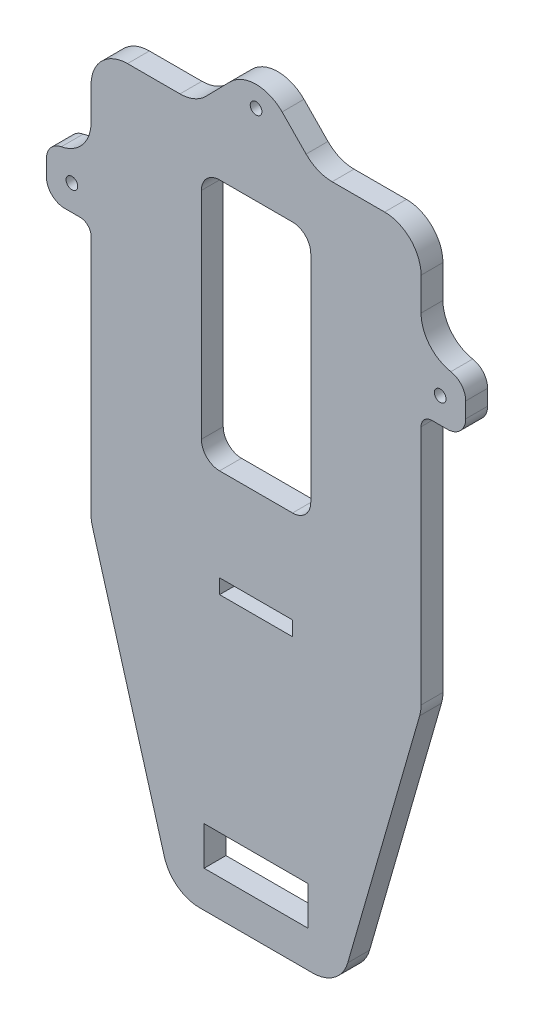
SolidWorks part; units mm, degrees
material "MDF"
ref_plane "Plano frontal" through (0, 0, 0) normal (0, 0, 1) x (1, 0, 0)
ref_plane "Plano superior" through (0, 0, 0) normal (0, 1, 0) x (1, 0, 0)
ref_plane "Plano direito" through (0, 0, 0) normal (1, 0, 0) x (0, 0, -1)
sketch "Esboço1" plane through (0, 0, 0) normal (0, 0, 1) x (1, 0, 0)
  line L1 (-45.25, -56.75) -> (45.25, -56.75) construction
  line L2 (-45.25, -56.75) -> (-45.25, 56.75) construction
  line L3 (-45.25, 56.75) -> (45.25, 56.75) construction
  line L4 (45.25, -56.75) -> (45.25, 13.75) construction
  line L5 (-45.25, -56.75) -> (45.25, 56.75) construction
  line L6 (-45.25, 56.75) -> (45.25, -56.75) construction
  line L18 (-45.25, -56.75) -> (21.552, -56.75) construction
  line L20 (-45.25, -56.75) -> (-23.0595, -133.85)
  line L21 (-23.0595, -133.85) -> (23.0595, -133.85)
  line L23 (14.25, -113.25) -> (-14.25, -113.25)
  line L24 (14.25, -113.25) -> (14.25, -123.85)
  line L25 (14.25, -123.85) -> (-14.25, -123.85)
  line L26 (-14.25, -113.25) -> (-14.25, -123.85)
  line L27 (14.25, -113.25) -> (-14.25, -123.85) construction
  line L28 (14.25, -123.85) -> (-14.25, -113.25) construction
  line L29 (-15.1, -125.35) -> (15.1, -125.35) construction
  line L30 (-15.1, -125.35) -> (-15.1, -111.75) construction
  line L31 (-15.1, -111.75) -> (15.1, -111.75) construction
  line L32 (15.1, -125.35) -> (15.1, -111.75) construction
  line L33 (-15.1, -125.35) -> (15.1, -111.75) construction
  line L34 (-15.1, -111.75) -> (15.1, -125.35) construction
  line L39 (-45.25, 27.75) -> (-45.25, 56.75)
  line L48 (15, -27.35) -> (-15, -27.35)
  line L50 (-45.25, 27.75) -> (-57.5, 27.75)
  line L52 (0, 0) -> (0, 36.35) construction
  line L54 (45.25, 27.75) -> (57.5, 27.75)
  line L55 (45.25, 27.75) -> (45.25, 56.75)
  line L56 (45.25, 27.75) -> (45.25, 56.75) construction
  line L57 (-45.25, 56.75) -> (-16.6633, 56.75)
  line L58 (-16.6633, 56.75) -> (0, 73.75)
  line L59 (0, 73.75) -> (16.6633, 56.75)
  line L60 (16.6633, 56.75) -> (45.25, 56.75)
  line L61 (-57.5, 27.75) -> (-57.5, 13.75)
  line L62 (-57.5, 13.75) -> (-45.25, 13.75)
  line L63 (57.5, 13.75) -> (45.25, 13.75)
  line L64 (57.5, 27.75) -> (57.5, 13.75)
  line L65 (23.0595, -133.85) -> (45.25, -56.75)
  line L66 (45.25, 13.75) -> (45.25, -56.75)
  line L67 (-45.25, -56.75) -> (-45.25, 13.75)
  line L68 (15, -27.35) -> (15, 41.75)
  line L69 (10, -52.75) -> (-10, -52.75)
  line L70 (10, -52.75) -> (10, -56.75)
  line L71 (10, -56.75) -> (-10, -56.75)
  line L72 (-10, -52.75) -> (-10, -56.75)
  line L73 (10, -52.75) -> (-10, -56.75) construction
  line L74 (10, -56.75) -> (-10, -52.75) construction
  line L75 (15, 41.75) -> (-15, 41.75)
  line L76 (-15, -27.35) -> (-15, 41.75)
  line L77 (15, -27.35) -> (-15, 41.75) construction
  line L78 (15, 41.75) -> (-15, -27.35) construction
  circle A0 centre (0, 63.75) radius 1.6
  circle A1 centre (-50.5, -80.53) radius 1.6
  circle A2 centre (-50.5, 20.75) radius 1.6
  circle A3 centre (50.5, 20.75) radius 1.6
  point P0 (0, 0)
  point P6 (0, -54.75)
  point P16 (0, -133.85)
  point P27 (0, -118.55)
  point P32 (0, -118.55)
  point P39 (0, 0)
  point P42 (0, 7.2)
  dimension "D3" = 3.2
  dimension "D10" = 10
  dimension "D4" = 7
  dimension "D5" = 10
  dimension "D9" = 43
  dimension "D19" = 101
  dimension "D1" = 90.5
  dimension "D2" = 113.5
  dimension "D6" = 7
  dimension "D7" = 55
  dimension "D8" = 10
  dimension "D11" = 28.5
  dimension "D12" = 10.6
  dimension "D13" = 13.6
  dimension "D14" = 30.2
  dimension "D15" = 7
  dimension "D16" = 144.28
  dimension "D17" = 25.4
  dimension "D18" = 7
  dimension "D20" = 15
  dimension "D21" = 20
  dimension "D22" = 7
  dimension "D23" = 4
  dimension "D24" = 30
extrude "Ressalto-extrusão1" add sketch "Esboço1" along normal blind 6 contours L23 L24 L25 | L26 L23 L25 A2 A1 A0 region at (0, -31.4719, 0)
fillet "Filete3" radius 3 2 edges at (45.25, 13.75, 3) (-45.25, 13.75, 3)
fillet "Filete4" radius 10 11 edges at (-16.6633, 56.75, 3) (16.6633, 56.75, 3) (-45.25, 27.75, 3) (45.25, 27.75, 3) (0, 73.75, 3) (45.25, 56.75, 3) (-45.25, 56.75, 3) (-45.25, -56.75, 3) (45.25, -56.75, 3) (23.0595, -133.85, 3) (-23.0595, -133.85, 3)
fillet "Filete5" radius 5 8 edges at (57.5, 13.75, 3) (57.5, 27.75, 3) (-57.5, 13.75, 3) (-57.5, 27.75, 3) (-15, -27.35, 3) (15, -27.35, 3) (15, 41.75, 3) (-15, 41.75, 3)
equation "\"mm\"=5"
